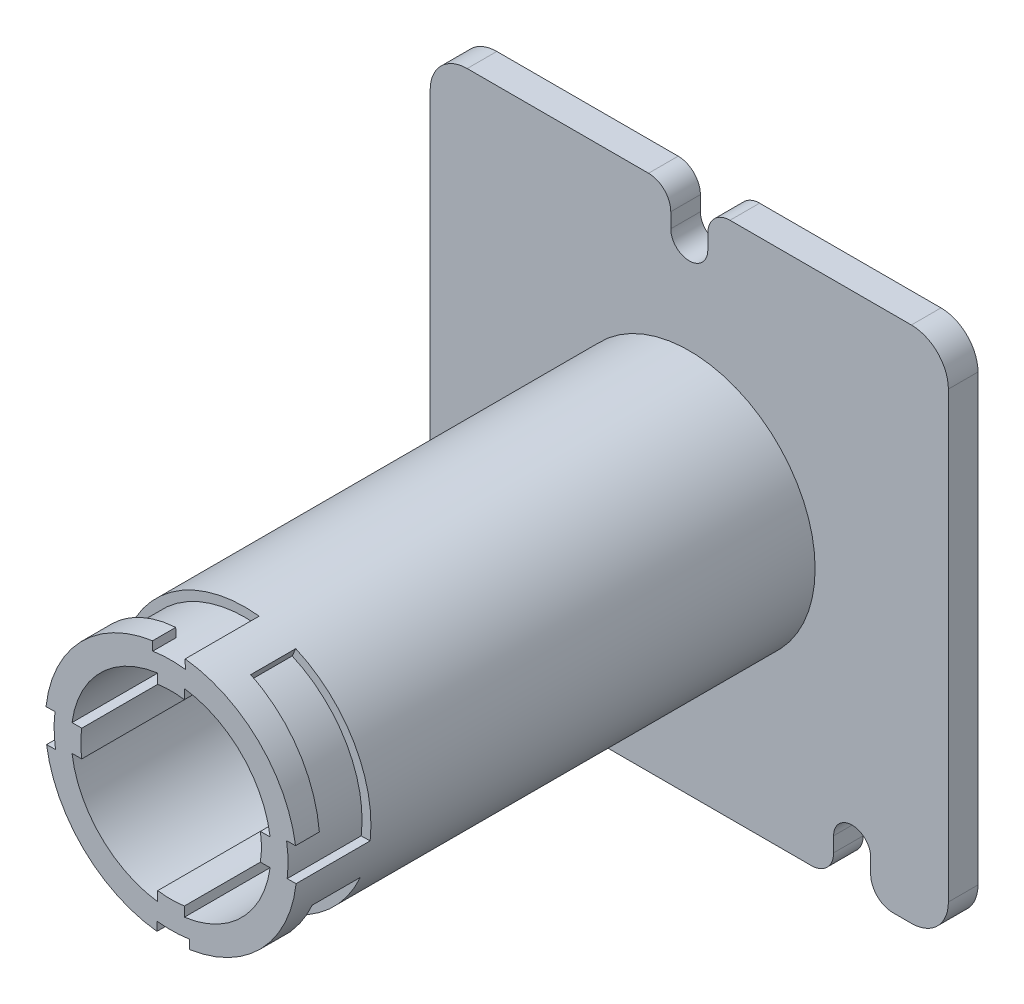
SolidWorks part; units mm, degrees
ref_plane "Front Plane" through (0, 0, 0) normal (0, 0, 1) x (1, 0, 0)
ref_plane "Top Plane" through (0, 0, 0) normal (0, 1, 0) x (1, 0, 0)
ref_plane "Right Plane" through (0, 0, 0) normal (1, 0, 0) x (0, 0, -1)
sketch "Sketch1" plane through (0, 0, 0) normal (0, 0, 1) x (1, 0, 0)
  circle A0 centre (0, 0) radius 13.5
  circle A1 centre (0, 0) radius 17
  dimension "D1" = 27
  dimension "D2" = 34
extrude "Boss-Extrude1" add sketch "Sketch1" along normal blind 70
sketch "Sketch2" plane through (0, 0, 0) normal (0, 0, -1) x (-1, 0, 0)
  line L0 (0, 0) -> (0, 63.6636) construction
  line L1 (0, 63.6636) -> (0, -68.8408) construction
  line L2 (0, 0) -> (102.4118, 0) construction
  line L3 (102.4118, 0) -> (-99.6614, 0) construction
  line L4 (-35, 35) -> (35, 35)
  line L5 (35, 35) -> (35, -35)
  line L6 (35, -35) -> (-35, -35)
  line L7 (-35, -35) -> (-35, 35)
  circle A0 centre (0, 0) radius 13.5
  dimension "D1" = 70
  dimension "D2" = 35
  dimension "D3" = 35
  dimension "D4" = 70
extrude "Boss-Extrude2" add sketch "Sketch2" along normal blind 4
sketch "Sketch3" plane through (0, 0, 70) normal (0, 0, 1) x (1, 0, 0)
  line L0 (0, 13.5) -> (0, -13.5) construction
  line L1 (0, 0) -> (13.5, 0) construction
  line L2 (13.5, 0) -> (-13.5, 0) construction
  line L3 (-1.8, 13.3795) -> (-1.8, 12.5718)
  line L4 (1.8, 13.3795) -> (1.8, 12.5718)
  line L5 (-13.3795, -1.8) -> (-12.5718, -1.8)
  line L6 (-13.3795, 1.8) -> (-12.5718, 1.8)
  line L7 (1.8, -12.5718) -> (1.8, -13.3795)
  line L8 (-1.8, -12.5718) -> (-1.8, -13.3795)
  line L13 (12.5718, 1.8) -> (13.3795, 1.8)
  line L14 (12.5718, -1.8) -> (13.3795, -1.8)
  circle A0 centre (0, 0) radius 13.5 construction
  arc A1 (1.8, 13.3795) -> (-1.8, 13.3795) centre (0, 0) ccw
  arc A2 (1.8, 12.5718) -> (-1.8, 12.5718) centre (0, 0) ccw
  arc A3 (-1.8, -13.3795) -> (1.8, -13.3795) centre (0, 0) ccw
  arc A4 (-13.3795, 1.8) -> (12.9101, 3.947) centre (0, 0) ccw
  arc A5 (-12.5718, 1.8) -> (-12.5718, -1.8) centre (0, 0) ccw
  arc A6 (-1.8, -12.5718) -> (1.8, -12.5718) centre (0, 0) ccw
  arc A7 (13.3795, -1.8) -> (-13.3795, -1.8) centre (0, 0) ccw
  arc A8 (12.5718, -1.8) -> (12.5718, 1.8) centre (0, 0) ccw
  circle M19 centre (0, 0) radius 13.5
  dimension "D1" = 25.4
  dimension "D2" = 1.8
  dimension "D3" = 1.8
  dimension "D4" = 1.8
  dimension "D5" = 1.8
extrude "Boss-Extrude3" add sketch "Sketch3" against normal blind 89 contours A5 L6 L5 M19 | A6 L8 L7 M19 | A8 L14 L13 M19 | A2 L4 L3 M19 region at (0, 13.0585, 70) region at (-13.0585, 0, 70) region at (13.0585, 0, 70) region at (0, -13.0585, 70)
sketch "Sketch4" plane through (0, 0, -4) normal (0, 0, -1) x (-1, 0, 0)
  circle A0 centre (0, 0) radius 13.5
  circle A2 centre (0, 0) radius 17
extrude "Boss-Extrude4" add sketch "Sketch4" along normal blind 15
fillet "Fillet1" radius 5 4 edges at (-35, -35, -2) (35, -35, -2) (35, 35, -2) (-35, 35, -2)
sketch "Sketch6" plane through (0, 0, -4) normal (0, 0, -1) x (-1, 0, 0)
  line L0 (0, 51.3569) -> (0, -75.6629) construction
  line L1 (-67.2572, 0) -> (147.6001, 0) construction
  line L2 (-2.5, 30) -> (-2.5, 35)
  line L3 (30, 35) -> (-30, 35) construction
  line L4 (-2.5, 35) -> (2.5, 35)
  line L5 (2.5, 35) -> (2.5, 30)
  line L6 (19.5, -30) -> (19.5, -35)
  line L7 (-30, -35) -> (30, -35) construction
  line L8 (19.5, -35) -> (24.5, -35)
  line L9 (24.5, -35) -> (24.5, -30)
  line L10 (-24.5, -30) -> (-24.5, -35)
  line L11 (-24.5, -35) -> (-19.5, -35)
  line L12 (-19.5, -35) -> (-19.5, -30)
  arc A0 (-2.5, 30) -> (2.5, 30) centre (0, 30) ccw
  arc A1 (-19.5, -30) -> (-24.5, -30) centre (-22, -30) ccw
  arc A2 (24.5, -30) -> (19.5, -30) centre (22, -30) ccw
  dimension "D1" = 5
  dimension "D3" = 5
  dimension "D4" = 5
  dimension "D2" = 30
  dimension "D5" = 30
  dimension "D6" = 30
  dimension "D7" = 22
  dimension "D8" = 22
extrude "Cut-Extrude1" cut sketch "Sketch6" against normal blind 4
fillet "Fillet2" radius 3 1 edges at (-2.5, 35, -2)
fillet "Fillet3" radius 3 1 edges at (2.5, 35, -2)
fillet "Fillet4" radius 3 1 edges at (19.5, -35, -2)
fillet "Fillet5" radius 3 1 edges at (-24.5, -35, -2)
fillet "Fillet6" radius 3 1 edges at (-19.5, -35, -2)
fillet "Fillet7" radius 3 1 edges at (24.5, -35, -2)
sketch "Sketch7" plane through (0, 0, 70) normal (0, 0, 1) x (1, 0, 0)
  line L0 (-1.8, 12.5718) -> (-1.8, 12.0665)
  line L1 (1.8, 12.5718) -> (1.8, 12.0665)
  line L2 (12.5718, 1.8) -> (12.0665, 1.8)
  line L3 (12.5718, -1.8) -> (12.0665, -1.8)
  line L4 (1.8, -12.5718) -> (1.8, -12.0665)
  line L5 (-1.8, -12.5718) -> (-1.8, -12.0665)
  line L6 (-12.5718, -1.8) -> (-12.0665, -1.8)
  line L7 (-12.5718, 1.8) -> (-12.0665, 1.8)
  arc A0 (-12.5718, 1.8) -> (-12.5718, -1.8) centre (0, 0) ccw
  arc A1 (-12.0665, 1.8) -> (-12.0665, -1.8) centre (0, 0) ccw
  arc A2 (1.8, 12.0665) -> (-1.8, 12.0665) centre (0, 0) ccw
  arc A3 (1.8, 12.5718) -> (-1.8, 12.5718) centre (0, 0) ccw
  arc A4 (12.0665, -1.8) -> (12.0665, 1.8) centre (0, 0) ccw
  arc A5 (12.5718, -1.8) -> (12.5718, 1.8) centre (0, 0) ccw
  arc A6 (-1.8, -12.0665) -> (1.8, -12.0665) centre (0, 0) ccw
  arc A7 (-1.8, -12.5718) -> (1.8, -12.5718) centre (0, 0) ccw
  dimension "D1" = 0.5
extrude "Boss-Extrude5" add sketch "Sketch7" against normal blind 89
sketch "Sketch8" plane through (0, 0, 70) normal (0, 0, 1) x (1, 0, 0)
  line L0 (-0.3697, 21.1824) -> (0.4142, -23.7277) construction
  line L1 (-21.7231, -0.3792) -> (21.7696, 0.38) construction
  line L2 (-2.4939, 16.8161) -> (-2.4727, 15.6053)
  line L3 (1.9055, 16.8929) -> (1.9266, 15.6821)
  line L4 (-16.8161, -2.4939) -> (-15.6053, -2.4727)
  line L5 (-16.8929, 1.9055) -> (-15.6821, 1.9266)
  line L6 (15.6821, -1.9266) -> (16.8929, -1.9055)
  line L10 (-1.9266, -15.6821) -> (-1.9055, -16.8929)
  line L11 (2.4727, -15.6053) -> (2.4939, -16.8161)
  line L13 (15.6053, 2.4727) -> (16.8161, 2.4939)
  arc A0 (15.6821, -1.9266) -> (15.6053, 2.4727) centre (0, 0) ccw
  arc A1 (16.8929, -1.9055) -> (16.8161, 2.4939) centre (0, 0) ccw
  arc A3 (-1.9055, -16.8929) -> (2.4939, -16.8161) centre (0, 0) ccw
  arc A4 (-1.9266, -15.6821) -> (2.4727, -15.6053) centre (0, 0) ccw
  arc A5 (1.9055, 16.8929) -> (-2.4939, 16.8161) centre (0, 0) ccw
  arc A6 (1.9266, 15.6821) -> (-2.4727, 15.6053) centre (0, 0) ccw
  arc A7 (-16.8929, 1.9055) -> (-16.8161, -2.4939) centre (0, 0) ccw
  arc A8 (-15.6821, 1.9266) -> (-15.6053, -2.4727) centre (0, 0) ccw
  point P13 (-2.2, 21.1856)
  point P14 (-2.2, -23.7314)
  point P15 (2.2, 21.1856)
  point P16 (2.2, -23.7314)
  point P17 (-21.7264, -2.2)
  point P18 (21.7729, -2.2)
  point P19 (-21.7264, 2.2)
  point P20 (21.7729, 2.2)
  dimension "D1" = 1.2
extrude "Cut-Extrude2" cut sketch "Sketch8" against normal blind 10
sketch "Sketch9" plane through (0, 0, -19) normal (0, 0, -1) x (-1, 0, 0)
  line L0 (-0.3697, 21.1824) -> (0.4142, -23.7277) construction
  line L1 (-21.7231, -0.3792) -> (21.7696, 0.38) construction
  line L2 (-2.4939, 16.8161) -> (-2.4727, 15.6053)
  line L3 (1.9055, 16.8929) -> (1.9266, 15.6821)
  line L4 (-16.8161, -2.4939) -> (-15.6053, -2.4727)
  line L5 (-16.8929, 1.9055) -> (-15.6821, 1.9266)
  line L6 (15.6821, -1.9266) -> (16.8929, -1.9055)
  line L7 (-1.9266, -15.6821) -> (-1.9055, -16.8929)
  line L8 (2.4727, -15.6053) -> (2.4939, -16.8161)
  line L9 (15.6053, 2.4727) -> (16.8161, 2.4939)
  arc A1 (16.8929, -1.9055) -> (16.8161, 2.4939) centre (0, 0) ccw
  arc A2 (-1.9055, -16.8929) -> (2.4939, -16.8161) centre (0, 0) ccw
  arc A3 (-1.9266, -15.6821) -> (2.4727, -15.6053) centre (0, 0) ccw
  arc A4 (1.9055, 16.8929) -> (-2.4939, 16.8161) centre (0, 0) ccw
  arc A5 (1.9266, 15.6821) -> (-2.4727, 15.6053) centre (0, 0) ccw
  arc A6 (-16.8929, 1.9055) -> (-16.8161, -2.4939) centre (0, 0) ccw
  arc A7 (-15.6821, 1.9266) -> (-15.6053, -2.4727) centre (0, 0) ccw
  arc A8 (15.6053, 2.4727) -> (15.6821, -1.9266) centre (0, 0) cw
extrude "Cut-Extrude3" cut sketch "Sketch9" against normal blind 10
sketch "Sketch10" plane through (0, 0, 60) normal (0, 0, 1) x (1, 0, 0)
  line L0 (0, 0) -> (-7.9575, -18.0899) construction
  line L1 (-6.3619, -14.4626) -> (-6.8451, -15.561)
  line L2 (-15.6053, -2.4727) -> (-16.8161, -2.4939)
  line L3 (2.4727, -15.6053) -> (2.4939, -16.8161)
  line L4 (0, 0) -> (18.0899, -7.9575) construction
  line L5 (14.4626, -6.3619) -> (15.561, -6.8451)
  line L6 (0, 0) -> (7.9575, 18.0899) construction
  line L7 (6.3619, 14.4626) -> (6.8451, 15.561)
  line L8 (15.6053, 2.4727) -> (16.8161, 2.4939)
  line L9 (0, 0) -> (-18.0899, 7.9575) construction
  line L10 (-2.4727, 15.6053) -> (-2.4939, 16.8161)
  line L11 (-14.4626, 6.3619) -> (-15.561, 6.8451)
  arc A0 (-15.6053, -2.4727) -> (-6.3619, -14.4626) centre (0, 0) ccw
  arc A1 (-16.8161, -2.4939) -> (-6.8451, -15.561) centre (0, 0) ccw
  arc A2 (-16.8161, -2.4939) -> (-1.9055, -16.8929) centre (0, 0) ccw construction
  arc A3 (2.4727, -15.6053) -> (14.4626, -6.3619) centre (0, 0) ccw
  arc A4 (2.4939, -16.8161) -> (15.561, -6.8451) centre (0, 0) ccw
  arc A5 (16.8161, 2.4939) -> (6.8451, 15.561) centre (0, 0) ccw
  arc A6 (15.6053, 2.4727) -> (6.3619, 14.4626) centre (0, 0) ccw
  arc A7 (-2.4727, 15.6053) -> (-14.4626, 6.3619) centre (0, 0) ccw
  arc A8 (-2.4939, 16.8161) -> (-15.561, 6.8451) centre (0, 0) ccw
  point P30 (0, 0)
extrude "Cut-Extrude4" cut sketch "Sketch10" along normal blind 6
sketch "Sketch11" plane through (0, 0, -9) normal (0, 0, -1) x (-1, 0, 0)
  line L0 (0, 0) -> (-7.9575, -18.0899) construction
  line L1 (-6.3619, -14.4626) -> (-6.8451, -15.561)
  line L2 (-15.6053, -2.4727) -> (-16.8161, -2.4939)
  line L3 (2.4727, -15.6053) -> (2.4939, -16.8161)
  line L4 (0, 0) -> (18.0899, -7.9575) construction
  line L5 (14.4626, -6.3619) -> (15.561, -6.8451)
  line L6 (0, 0) -> (7.9575, 18.0899) construction
  line L7 (6.3619, 14.4626) -> (6.8451, 15.561)
  line L8 (15.6053, 2.4727) -> (16.8161, 2.4939)
  line L9 (0, 0) -> (-18.0899, 7.9575) construction
  line L10 (-2.4727, 15.6053) -> (-2.4939, 16.8161)
  line L11 (-14.4626, 6.3619) -> (-15.561, 6.8451)
  arc A0 (-15.6053, -2.4727) -> (-6.3619, -14.4626) centre (0, 0) ccw
  arc A1 (-16.8161, -2.4939) -> (-6.8451, -15.561) centre (0, 0) ccw
  arc A2 (2.4727, -15.6053) -> (14.4626, -6.3619) centre (0, 0) ccw
  arc A3 (2.4939, -16.8161) -> (15.561, -6.8451) centre (0, 0) ccw
  arc A4 (16.8161, 2.4939) -> (6.8451, 15.561) centre (0, 0) ccw
  arc A5 (15.6053, 2.4727) -> (6.3619, 14.4626) centre (0, 0) ccw
  arc A6 (-2.4727, 15.6053) -> (-14.4626, 6.3619) centre (0, 0) ccw
  arc A7 (-2.4939, 16.8161) -> (-15.561, 6.8451) centre (0, 0) ccw
extrude "Cut-Extrude6" cut sketch "Sketch11" along normal blind 6
chamfer "Chamfer1" distance 10 angle 5 1 edges at (-2.4833, 16.2107, 66) first distance on face at (-9.3636, 12.2105, 66)
sketch "Sketch12" plane through (0, 0, 66) normal (0, 0, -1) x (-1, 0, 0)
  line L0 (15.561, 6.8451) -> (0, 0) construction
  line L1 (-15.561, -6.8451) -> (0, 0) construction
  line L2 (12.7468, 11.2481) -> (11.8103, 10.4955)
  line L3 (-12.8966, -11.0761) -> (-11.9607, -10.3239)
  line L4 (12.4048, 11.6242) -> (12.3734, 9.8255)
  line L5 (14.4626, 6.3619) -> (15.561, 6.8451)
  line L7 (14.4626, 6.3619) -> (15.561, 6.8451)
  line L8 (-14.4626, -6.3619) -> (-15.561, -6.8451)
  arc A0 (-15.561, -6.8451) -> (-12.8966, -11.0761) centre (0, 0) ccw
  arc A1 (-14.4626, -6.3619) -> (-11.9607, -10.3239) centre (0, 0) ccw
  arc A4 (15.561, 6.8451) -> (12.4048, 11.6242) centre (0, 0) ccw
  arc A5 (14.4626, 6.3619) -> (12.3734, 9.8255) centre (0, 0) ccw
  arc A6 (15.561, 6.8451) -> (12.7468, 11.2481) centre (0, 0) ccw
  arc A7 (14.4626, 6.3619) -> (11.8103, 10.4955) centre (0, 0) ccw
  dimension "D1" = 0
extrude "Cut-Extrude7" cut sketch "Sketch12" against normal blind 0.5
chamfer "Chamfer2" distance 10 angle 5 1 edges at (2.4833, -16.2107, 66) first distance on face at (7.7024, -13.9001, 66)
sketch "Sketch13" plane through (0, 0, -15) normal (0, 0, 1) x (1, 0, 0)
  line L0 (15.561, 6.8451) -> (0, 0) construction
  line L1 (-15.561, -6.8451) -> (0, 0) construction
  line L2 (12.7468, 11.2481) -> (11.8103, 10.4955)
  line L3 (-12.8966, -11.0761) -> (-11.9607, -10.3239)
  line L4 (14.4626, 6.3619) -> (15.561, 6.8451)
  line L5 (-14.4626, -6.3619) -> (-15.561, -6.8451)
  arc A0 (-15.561, -6.8451) -> (-12.8966, -11.0761) centre (0, 0) ccw
  arc A1 (-14.4626, -6.3619) -> (-11.9607, -10.3239) centre (0, 0) ccw
  arc A2 (15.561, 6.8451) -> (12.7468, 11.2481) centre (0, 0) ccw
  arc A3 (14.4626, 6.3619) -> (11.8103, 10.4955) centre (0, 0) ccw
extrude "Cut-Extrude8" cut sketch "Sketch13" against normal blind 0.5
chamfer "Chamfer3" distance 10 angle 5 1 edges at (-2.4833, -16.2107, -15) first distance on face at (-7.7024, -13.9001, -15)
chamfer "Chamfer4" distance 10 angle 5 1 edges at (2.4833, 16.2107, -15) first distance on face at (7.6149, 13.9705, -15)
chamfer "Chamfer5" distance 1.2 angle 25 1 edges at (12.1018, 10.7297, -15.0251) first distance on face at (8.4915, 13.4308, -15.3451)
chamfer "Chamfer6" distance 1.2 angle 25 1 edges at (-12.1744, -10.4956, -15.0184) first distance on face at (-8.5255, -13.3433, -15.342)
chamfer "Chamfer7" distance 15 angle 3 1 edges at (16.2107, -2.4833, -15) first distance on face at (12.2105, -9.3636, -15)
chamfer "Chamfer8" distance 15 angle 3 1 edges at (-16.2107, 2.4833, -15) first distance on face at (-12.2105, 9.3636, -15)
chamfer "Chamfer9" distance 15 angle 3 1 edges at (-16.2107, -2.4833, 66) first distance on face at (-12.2105, -9.3636, 66)
chamfer "Chamfer10" distance 15 angle 3 1 edges at (16.2107, 2.4833, 66) first distance on face at (12.2105, 9.3636, 66)
chamfer "Chamfer11" distance 1.2 angle 25 1 edges at (12.1744, -10.4956, 66.0184) first distance on face at (8.5255, -13.3433, 66.342)
chamfer "Chamfer12" distance 1.2 angle 25 1 edges at (-12.1018, 10.7297, 66.0251) first distance on face at (-8.4915, 13.4308, 66.3451)
